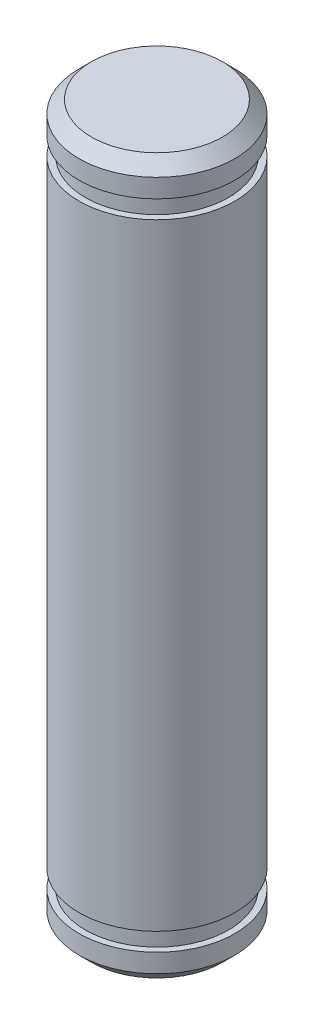
SolidWorks part; units mm, degrees
ref_plane "Front" through (0, 0, 0) normal (0, 0, 1) x (1, 0, 0)
ref_plane "Top" through (0, 0, 0) normal (0, 1, 0) x (1, 0, 0)
ref_plane "Right" through (0, 0, 0) normal (1, 0, 0) x (0, 0, -1)
ref_axis "side-side" through (80.9, 0, 0) along (-1, 0, 0)
ref_axis "up-down" through (0, 50, 0) along (0, -1, 0)
ref_axis "front-back" through (0, 0, -80.9) along (0, 0, 1)
sketch "Sketch1" plane through (0, 0, 0) normal (0, 0, 1) x (1, 0, 0)
  line L0 (-3.175, 12.5603) -> (-3.175, -12.5603)
  line L1 (0, 14.5669) -> (-3.175, 14.5669)
  line L2 (0, 14.5669) -> (0, -14.5669)
  line L3 (0, -14.5669) -> (-3.175, -14.5669)
  line L4 (-3.175, 14.5669) -> (-3.175, 13.2969)
  line L5 (-3.175, 13.2969) -> (-2.921, 13.2969)
  line L6 (-3.175, -13.2969) -> (-3.175, -14.5669)
  line L7 (-3.175, 12.5603) -> (-2.921, 12.5603)
  line L8 (-2.921, 13.2969) -> (-2.921, 12.5603)
  line L9 (-3.175, -12.5603) -> (-2.921, -12.5603)
  line L10 (0, 14.5669) -> (0, 13.3378) construction
  line L11 (-3.175, -13.2969) -> (-2.921, -13.2969)
  line L12 (-2.921, -12.5603) -> (-2.921, -13.2969)
  line L13 (-3.175, -11.7983) -> (3.175, -11.7983) construction
  dimension "D1" = 6.35
  dimension "D2" = 0.7366
  dimension "D3" = 1.27
  dimension "D4" = 25.1206
  dimension "D5" = 0.254
  dimension "D6" = 0.762
revolve "Revolve1" add sketch "Sketch1" angle 360 about L10
chamfer "Chamfer1" distance 0.508 angle 45 2 edges at (-3.175, -14.5669, 0) (-3.175, 14.5669, 0)
